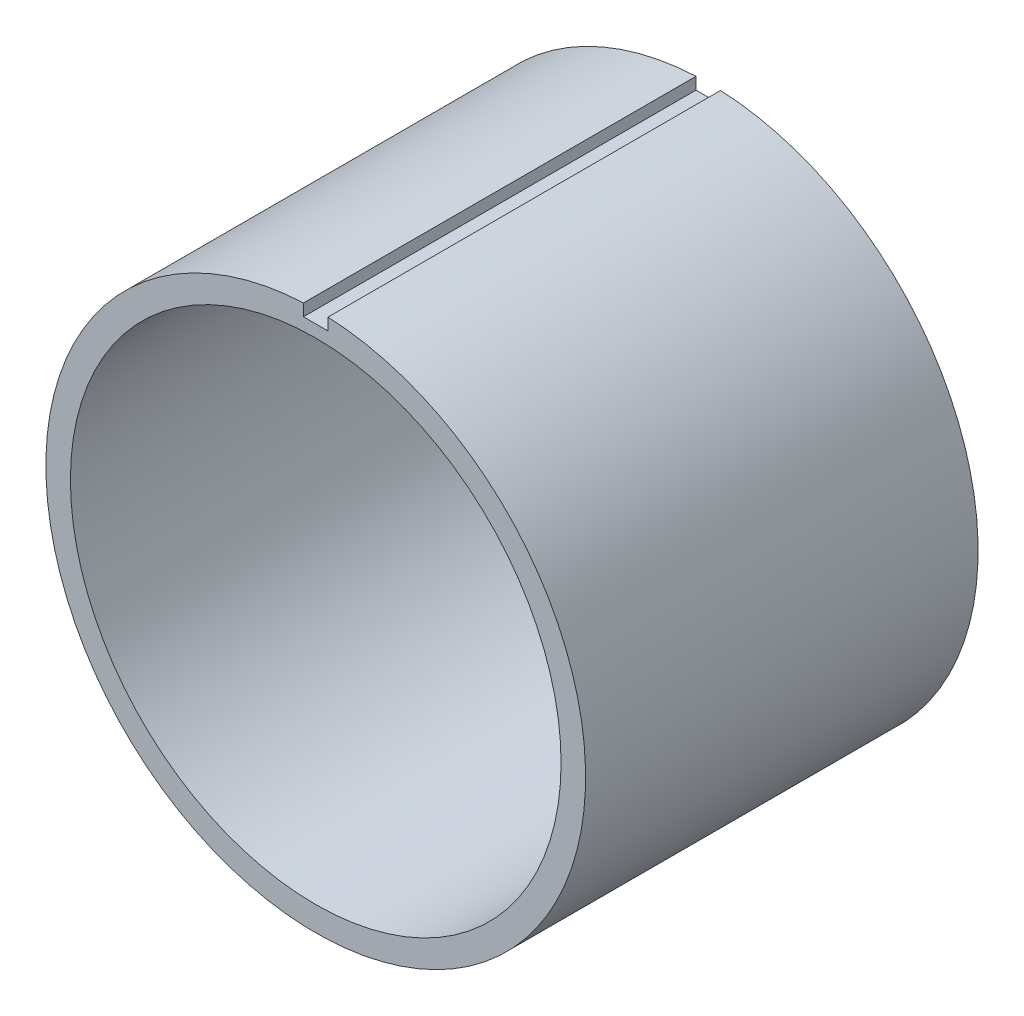
SolidWorks part; units mm, degrees
ref_plane "Front Plane" through (0, 0, 0) normal (0, 0, 1) x (1, 0, 0)
ref_plane "Top Plane" through (0, 0, 0) normal (0, 1, 0) x (1, 0, 0)
ref_plane "Right Plane" through (0, 0, 0) normal (1, 0, 0) x (0, 0, -1)
sketch "Sketch1" plane through (0, 0, 0) normal (0, 0, 1) x (1, 0, 0)
  circle A0 centre (0, 0) radius 110
  circle A1 centre (0, 0) radius 100
  dimension "D1" = 220
  dimension "D2" = 200
extrude "Boss-Extrude1" add sketch "Sketch1" along normal blind 150
sketch "Sketch2" plane through (0, 0, 0) normal (0, 0, -1) x (-1, 0, 0)
  line L0 (0, 40) -> (0, 100)
  line L1 (0, 100) -> (5, 99.8749)
  line L2 (5, 99.8749) -> (5, 40)
  line L3 (5, 40) -> (0, 40)
  line L4 (40, 0) -> (100, 0)
  line L5 (99.8749, -5) -> (40, -5)
  line L6 (40, -5) -> (40, 0)
  line L7 (100, 0) -> (99.8749, -5)
  line L8 (0, -40) -> (0, -100)
  line L9 (-5, -99.8749) -> (-5, -40)
  line L10 (-5, -40) -> (0, -40)
  line L11 (0, -100) -> (-5, -99.8749)
  line L12 (-40, 0) -> (-100, 0)
  line L13 (-99.8749, 5) -> (-40, 5)
  line L14 (-40, 5) -> (-40, 0)
  line L15 (-100, 0) -> (-99.8749, 5)
  circle A0 centre (0, 0) radius 45
  circle A1 centre (0, 0) radius 40
  circle A2 centre (0, 0) radius 110
  circle A3 centre (0, 0) radius 100
  circle M1 centre (0, 0) radius 110
  circle M2 centre (0, 0) radius 100
  dimension "D1" = 220
  dimension "D2" = 200
  dimension "D3" = 90
  dimension "D4" = 80
  dimension "D5" = 60
  dimension "D6" = 5
  dimension "D7" = 5
extrude "Boss-Extrude2" add sketch "Sketch2" along normal blind 10 contours M1 M2 | A0 L13 L15 L12 | L13 A0 L12 L14 | A1 L0 A0 L13 L14 | A1 L12 A0 L9 L10 | A0 L9 L11 L8 | L9 A0 L8 L10 | A1 L8 A0 L5 L6 | A0 L5 L7 L4 | L5 A0 L4 L6 | A1 L4 A0 L2 L3 | A0 L2 L1 L0 | L2 A0 L0 L3 region at (28.7329, 28.7329, 0) region at (-2.4764, 42.4543, 0) region at (-2.5, 39.9366, 0) region at (-2.5012, 72.4223, 0) region at (-42.4543, -2.4764, 0) region at (-39.9366, -2.5, 0) region at (28.7329, -28.7329, 0) region at (42.4543, 2.4764, 0) region at (72.4223, 2.5012, 0) region at (-72.4223, -2.5012, 0) region at (2.4764, -42.4543, 0) region at (2.5012, -72.4223, 0) region at (106.8887, 0, 0)
ref_plane "Plane1" through (0, 105, 0) normal (0, 1, 0) x (-1, 0, 0)
sketch "Sketch4" plane through (0, 105, 0) normal (0, 1, 0) x (-1, 0, 0)
  line L1 (0, 341.9402) -> (0, -108.536) construction
  line L2 (-5, 150) -> (5, 150)
  line L3 (100, 150) -> (-100, 150) construction
  line L4 (110, 150) -> (-110, 150) construction
  line L6 (5, 150) -> (5, -10)
  line L7 (-110, -10) -> (110, -10) construction
  line L8 (5, -10) -> (-5, -10)
  line L9 (-5, -10) -> (-5, 150)
  dimension "D1" = 5
  dimension "D2" = 5
extrude "Cut-Extrude1" cut sketch "Sketch4" along normal blind 10
